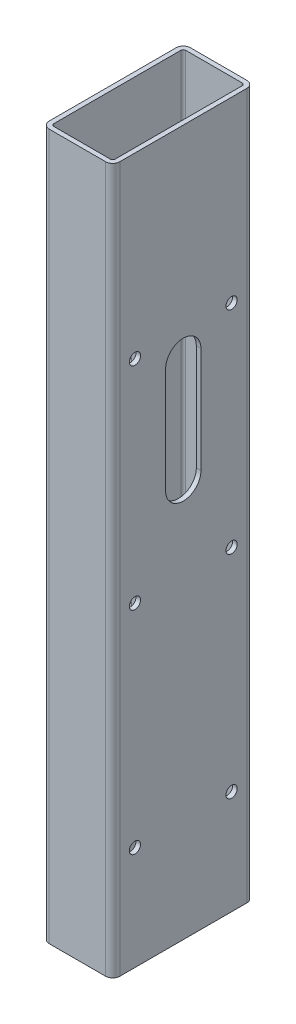
SolidWorks part; units mm, degrees
material "6061-T6 (SS)"
ref_plane "Front Plane" through (0, 0, 0) normal (0, 0, 1) x (1, 0, 0)
ref_plane "Top Plane" through (0, 0, 0) normal (0, 1, 0) x (1, 0, 0)
ref_plane "Right Plane" through (0, 0, 0) normal (1, 0, 0) x (0, 0, -1)
sketch "Sketch1" plane through (0, 0, 0) normal (0, 1, 0) x (1, 0, 0)
  line L1 (10.16, -25.4) -> (-10.16, -25.4)
  line L2 (12.7, -22.86) -> (12.7, 22.86)
  line L3 (10.16, 25.4) -> (-10.16, 25.4)
  line L4 (-12.7, -22.86) -> (-12.7, 22.86)
  line L5 (12.7, -25.4) -> (-12.7, 25.4) construction
  line L6 (12.7, 25.4) -> (-12.7, -25.4) construction
  arc A0 (-10.16, -25.4) -> (-12.7, -22.86) centre (-10.16, -22.86) cw
  arc A1 (10.16, -25.4) -> (12.7, -22.86) centre (10.16, -22.86) ccw
  arc A2 (12.7, 22.86) -> (10.16, 25.4) centre (10.16, 22.86) ccw
  arc A3 (-10.16, 25.4) -> (-12.7, 22.86) centre (-10.16, 22.86) ccw
  point P0 (0, 0)
  dimension "D3" = 2.54
  dimension "D1" = 25.4
  dimension "D2" = 50.8
extrude "Extrude-Thin1" add sketch "Sketch1" against normal blind 254 thin thin type one direction reverse wall 1.651
sketch "Sketch2" plane through (-12.7, 0, 0) normal (-1, 0, 0) x (0, 0, 1)
  line L0 (0, -72.7955) -> (0, -207.946) construction
  line L3 (-128.814, -353.996) -> (-122.464, -353.996) construction
  line L4 (6.6675, -72.7955) -> (6.6675, -207.946)
  line L5 (-6.6675, -72.7955) -> (-6.6675, -207.946)
  line L6 (-263.9645, -353.996) -> (-128.814, -353.996) construction
  line L7 (-128.814, -353.996) -> (0, -77.7533) construction
  line L8 (0, -201.596) -> (-263.9645, -353.996) construction
  arc A2 (6.6675, -72.7955) -> (-6.6675, -72.7955) centre (0, -72.7955) ccw
  arc A3 (-6.6675, -207.946) -> (6.6675, -207.946) centre (0, -207.946) ccw
  arc A4 (-122.464, -360.6635) -> (-122.464, -347.3285) centre (-122.464, -353.996) ccw construction
  point P3 (0, -140.3707)
  dimension "D5" = 13.335
  dimension "D2" = 65
  dimension "D3" = 30
  dimension "D4" = 304.8
  dimension "D6" = 6.35
extrude "Cut-Extrude1" cut sketch "Sketch2" against normal up to next
sketch "Sketch5" plane through (12.7, 0, 0) normal (1, 0, 0) x (0, 0, -1)
  line L0 (0, -72.7955) -> (0, -110.8955) construction
  line L1 (6.35, -72.7955) -> (6.35, -110.8955)
  line L2 (-6.35, -72.7955) -> (-6.35, -110.8955)
  arc A0 (6.35, -72.7955) -> (-6.35, -72.7955) centre (0, -72.7955) ccw
  arc A1 (-6.35, -110.8955) -> (6.35, -110.8955) centre (0, -110.8955) ccw
  arc A2 (6.6675, -72.7955) -> (-6.6675, -72.7955) centre (0, -72.7955) ccw construction
  point P2 (0, -91.8455)
  dimension "D1" = 6.35
  dimension "D2" = 38.1
extrude "Cut-Extrude4" cut sketch "Sketch5" against normal up to next
sketch "Sketch4" plane through (12.7, 0, 0) normal (1, 0, 0) x (0, 0, -1)
  circle A0 centre (-17.399, -216.5707) radius 2.0193 construction
  circle A1 centre (17.399, -216.5707) radius 2.0193 construction
  circle A2 centre (-17.399, -140.3707) radius 2.0193 construction
  circle A3 centre (17.399, -140.3707) radius 2.0193 construction
  circle A4 centre (-17.399, -64.1707) radius 2.0193 construction
  circle A5 centre (17.399, -64.1707) radius 2.0193 construction
  circle A6 centre (-17.399, -216.5707) radius 2.0193
  circle A7 centre (17.399, -216.5707) radius 2.0193
  circle A8 centre (-17.399, -140.3707) radius 2.0193
  circle A9 centre (17.399, -140.3707) radius 2.0193
  circle A10 centre (-17.399, -64.1707) radius 2.0193
  circle A11 centre (17.399, -64.1707) radius 2.0193
extrude "Cut-Extrude3" cut sketch "Sketch4" against normal through all
